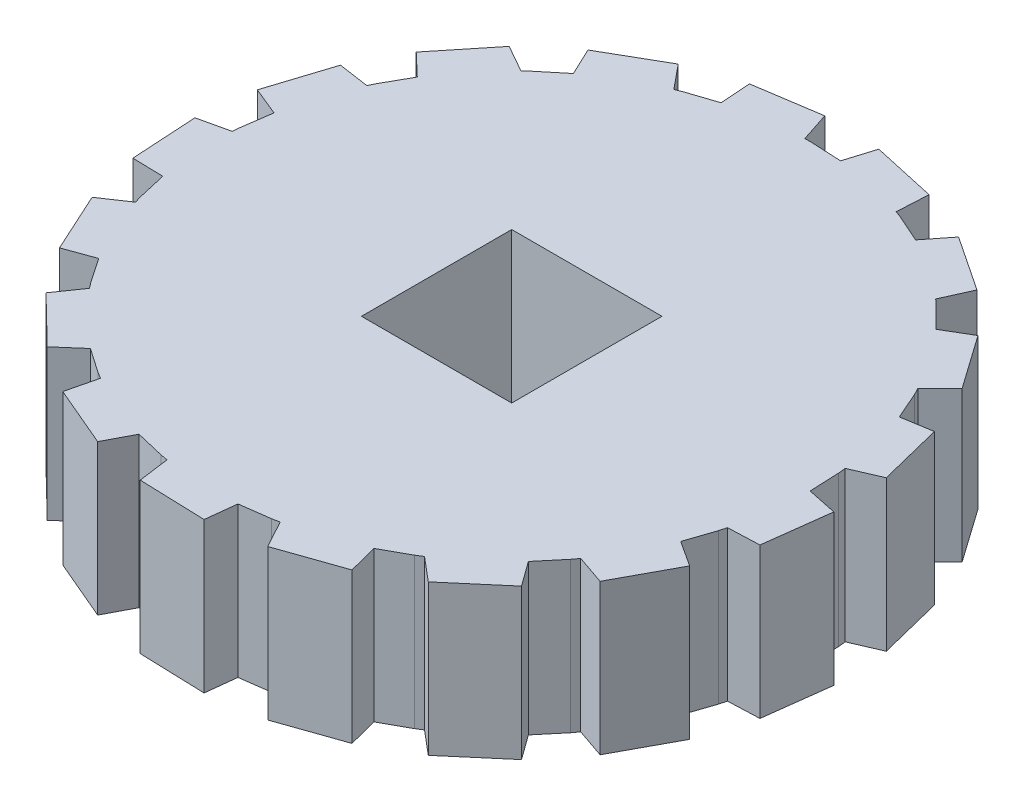
SolidWorks part; units mm, degrees
ref_plane "Front Plane" through (0, 0, 0) normal (0, 0, 1) x (1, 0, 0)
ref_plane "Top Plane" through (0, 0, 0) normal (0, 1, 0) x (1, 0, 0)
ref_plane "Right Plane" through (0, 0, 0) normal (1, 0, 0) x (0, 0, -1)
sketch "Belt Pulley" plane through (0, 0, 0) normal (0, 1, 0) x (1, 0, 0)
  line L0 (0, -18.2889) -> (0, 17.4478) construction
  line L1 (-3.175, -3.175) -> (3.175, -3.175)
  line L2 (-3.175, -3.175) -> (-3.175, 3.175)
  line L3 (-3.175, 3.175) -> (3.175, 3.175)
  line L4 (3.175, -3.175) -> (3.175, 3.175)
  line L5 (-3.175, -3.175) -> (3.175, 3.175) construction
  line L6 (-3.175, 3.175) -> (3.175, -3.175) construction
  line L7 (0, 12.7) -> (1.26, 12.6373)
  line L8 (1.26, 12.6373) -> (0, 0) construction
  line L9 (1.26, 12.6373) -> (1.64, 13.8734) construction
  line L10 (1.64, 13.8734) -> (4.368, 13.2696)
  line L11 (4.368, 13.2696) -> (4.7273, 13.1459) construction
  line L12 (0, 0) -> (4.7273, 13.1459) construction
  line L13 (8.8665, 10.7956) -> (8.3244, 9.5913)
  line L14 (1.26, 12.6373) -> (1.64, 13.8734)
  line L15 (4.368, 13.2696) -> (4.2975, 11.9508)
  line L16 (6.5409, 12.3441) -> (8.8665, 10.7956)
  line L17 (5.74, 11.3288) -> (6.5409, 12.3441)
  line L18 (4.5878, 11.8424) -> (5.74, 11.3288)
  line L19 (12.1676, 6.8637) -> (11.2271, 5.9365)
  line L20 (10.5584, 9.1477) -> (12.1676, 6.8637)
  line L21 (9.4449, 8.4903) -> (10.5584, 9.1477)
  line L22 (8.5559, 9.3854) -> (9.4449, 8.4903)
  line L23 (13.8254, 2.0047) -> (12.6135, 1.4799)
  line L24 (13.15, 4.7158) -> (13.8254, 2.0047)
  line L25 (11.8741, 4.505) -> (13.15, 4.7158)
  line L26 (11.3686, 5.6609) -> (11.8741, 4.505)
  line L27 (13.616, -3.125) -> (12.2963, -3.1765)
  line L28 (13.9655, -0.3529) -> (13.616, -3.125)
  line L29 (12.6997, -0.0886) -> (13.9655, -0.3529)
  line L30 (12.6458, 1.1718) -> (12.6997, -0.0886)
  line L31 (11.5677, -7.8326) -> (10.3185, -7.404)
  line L32 (12.895, -5.374) -> (11.5677, -7.8326)
  line L33 (11.8101, -4.6703) -> (12.895, -5.374)
  line L34 (12.2152, -3.4755) -> (11.8101, -4.6703)
  line L35 (7.9571, -11.4824) -> (6.9471, -10.6315)
  line L36 (10.0829, -9.6693) -> (7.9571, -11.4824)
  line L37 (9.3255, -8.6212) -> (10.0829, -9.6693)
  line L38 (10.1348, -7.6535) -> (9.3255, -8.6212)
  line L39 (3.2718, -13.5815) -> (2.6375, -12.4231)
  line L40 (5.909, -12.6588) -> (3.2718, -13.5815)
  line L41 (5.5814, -11.4078) -> (5.909, -12.6588)
  line L42 (6.6857, -10.7978) -> (5.5814, -11.4078)
  line L43 (-1.8553, -13.8463) -> (-2.0284, -12.537)
  line L44 (0.9372, -13.9385) -> (-1.8553, -13.8463)
  line L45 (1.0836, -12.6537) -> (0.9372, -13.9385)
  line L46 (2.3336, -12.4838) -> (1.0836, -12.6537)
  line L47 (-6.7319, -12.241) -> (-6.4203, -10.9576)
  line L48 (-4.1613, -13.3358) -> (-6.7319, -12.241)
  line L49 (-3.5607, -12.1906) -> (-4.1613, -13.3358)
  line L50 (-2.3336, -12.4838) -> (-3.5607, -12.1906)
  line L51 (-10.6993, -8.9826) -> (-9.9451, -7.8984)
  line L52 (-8.6978, -10.9321) -> (-10.6993, -8.9826)
  line L53 (-7.724, -10.0812) -> (-8.6978, -10.9321)
  line L54 (-6.6857, -10.7978) -> (-7.724, -10.0812)
  line L55 (-13.2216, -4.511) -> (-12.1268, -3.7725)
  line L56 (-12.0595, -7.0518) -> (-13.2216, -4.511)
  line L57 (-10.8441, -6.6102) -> (-12.0595, -7.0518)
  line L58 (-10.1348, -7.6535) -> (-10.8441, -6.6102)
  line L59 (-13.9584, 0.5698) -> (-12.6706, 0.863)
  line L60 (-13.7926, -2.2192) -> (-13.9584, 0.5698)
  line L61 (-12.4997, -2.2465) -> (-13.7926, -2.2192)
  line L62 (-12.2152, -3.4755) -> (-12.4997, -2.2465)
  line L63 (-12.8099, 5.5737) -> (-11.5033, 5.3819)
  line L64 (-13.6629, 2.9131) -> (-12.8099, 5.5737)
  line L65 (-12.4672, 2.4207) -> (-13.6629, 2.9131)
  line L66 (-12.6458, 1.1718) -> (-12.4672, 2.4207)
  line L67 (-9.9315, 9.8248) -> (-8.7823, 9.1739)
  line L68 (-11.6879, 7.652) -> (-9.9315, 9.8248)
  line L69 (-10.7509, 6.7609) -> (-11.6879, 7.652)
  line L70 (-11.3686, 5.6609) -> (-10.7509, 6.7609)
  line L71 (-5.7117, 12.749) -> (-4.8753, 11.727)
  line L72 (-8.1345, 11.3574) -> (-5.7117, 12.749)
  line L73 (-7.5826, 10.188) -> (-8.1345, 11.3574)
  line L74 (-8.5559, 9.3854) -> (-7.5826, 10.188)
  line L75 (-0.7205, 13.9514) -> (-0.3098, 12.6962)
  line L76 (-3.4824, 13.529) -> (-0.7205, 13.9514)
  line L77 (-3.3902, 12.2391) -> (-3.4824, 13.529)
  line L78 (-4.5878, 11.8424) -> (-3.3902, 12.2391)
  arc A0 (0, 12.7) -> (-0.3098, 12.6962) centre (0, 0) ccw
  circle A1 centre (0, 0) radius 13.97 construction
  arc A2 (-3.3902, 12.2391) -> (-4.8753, 11.727) centre (0, 0) ccw
  arc A3 (-7.5826, 10.188) -> (-8.7823, 9.1739) centre (0, 0) ccw
  arc A4 (5.74, 11.3288) -> (4.2975, 11.9508) centre (0, 0) ccw
  arc A5 (9.4449, 8.4903) -> (8.3244, 9.5913) centre (0, 0) ccw
  arc A6 (11.8741, 4.505) -> (11.2271, 5.9365) centre (0, 0) ccw
  arc A7 (12.6997, -0.0886) -> (12.6135, 1.4799) centre (0, 0) ccw
  arc A8 (11.8101, -4.6703) -> (12.2963, -3.1765) centre (0, 0) ccw
  arc A9 (-10.7509, 6.7609) -> (-11.5033, 5.3819) centre (0, 0) ccw
  arc A10 (-12.4672, 2.4207) -> (-12.6706, 0.863) centre (0, 0) ccw
  arc A11 (-12.4997, -2.2465) -> (-12.1268, -3.7725) centre (0, 0) ccw
  arc A12 (-10.8441, -6.6102) -> (-9.9451, -7.8984) centre (0, 0) ccw
  arc A13 (-7.724, -10.0812) -> (-6.4203, -10.9576) centre (0, 0) ccw
  arc A14 (-3.5607, -12.1906) -> (-2.0284, -12.537) centre (0, 0) ccw
  arc A15 (1.0836, -12.6537) -> (2.6375, -12.4231) centre (0, 0) ccw
  arc A16 (5.5814, -11.4078) -> (6.9471, -10.6315) centre (0, 0) ccw
  arc A17 (9.3255, -8.6212) -> (10.3185, -7.404) centre (0, 0) ccw
  point P98 (0, 0)
  dimension "D1" = 25.4
  dimension "D9" = 27.94
  dimension "D2" = 6.35
  dimension "D3" = 6.35
  dimension "D4" = 0.38
  dimension "D5" = 2.794
  dimension "D6" = 1.26
  dimension "D7" = 0.38
  dimension "D8" = 17
extrude "Boss-Extrude1" add sketch "Belt Pulley" along normal blind 6.35 contours A0 L4 L1 L2 L3 region at (0.6104, 0, -12.2745)
equation "\"Ball Diameter\"= 1.75in"
equation "\"Sheet Thickness\"= 0.25in"
equation "\"Screw Diameter\"= .17in"
equation "\"Robot Diameter\"= 14in"
equation "\"Castor Screw Diameter\"= 0.22in"
equation "\"Wheel Diameter\" = 4in"
equation "\"Nut Diameter\" = 8.4mm"
equation "\"Nut Height\" = 2.9mm"
equation "\"Screw Height\" = 0.55in"
equation "\"Pulley Diameter\" = 1in"
equation "\"Reactor Height\" = 14in"
equation "\"D1@Belt Pulley\"=\"Pulley Diameter\""
equation "\"D2@Belt Pulley\"=\"Sheet Thickness\""
equation "\"D3@Belt Pulley\"=\"Sheet Thickness\""
equation "\"D1@Boss-Extrude1\"=\"Sheet Thickness\""
equation "\"D9@Belt Pulley\"=\"Pulley Diameter\" + 0.1in"
